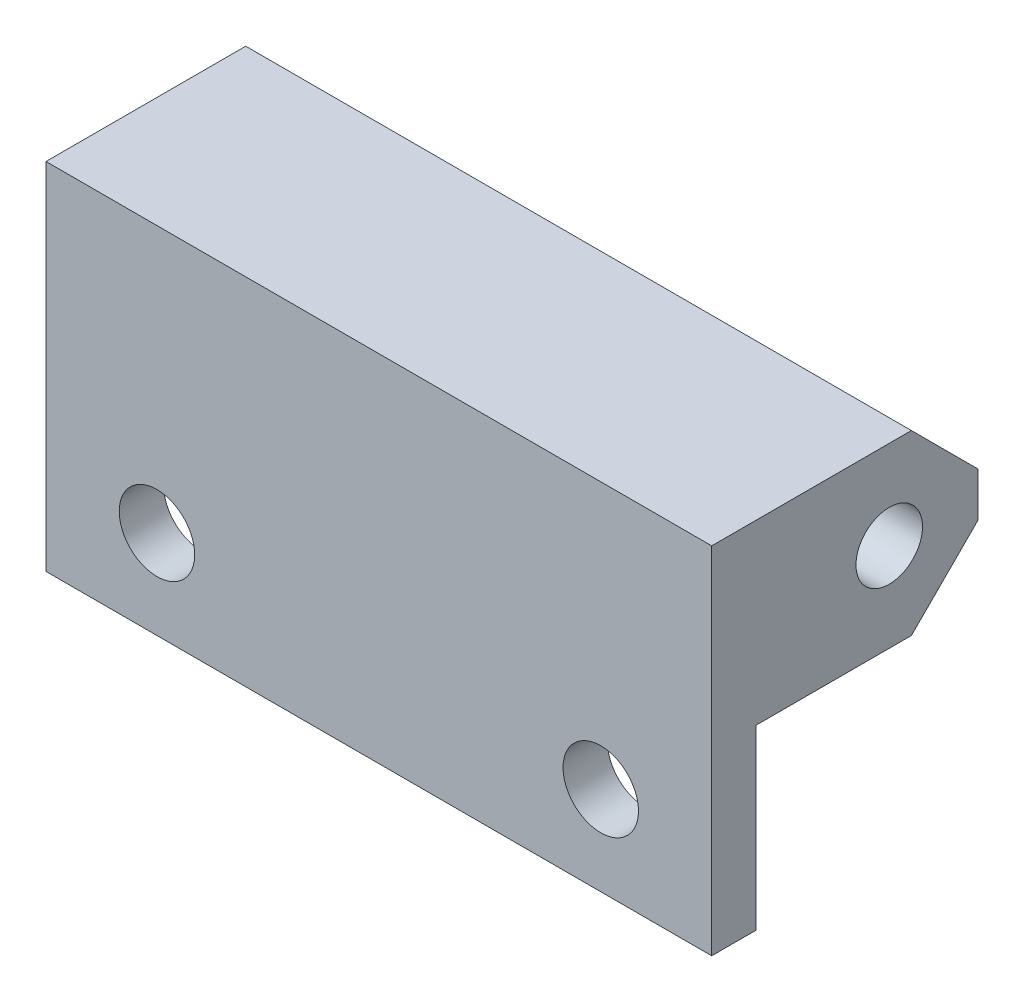
SolidWorks part; units mm, degrees
material "6061 Alloy"
ref_plane "Front Plane" through (0, 0, 0) normal (0, 0, 1) x (1, 0, 0)
ref_plane "Top Plane" through (0, 0, 0) normal (0, 1, 0) x (1, 0, 0)
ref_plane "Right Plane" through (0, 0, 0) normal (1, 0, 0) x (0, 0, -1)
sketch "Sketch1" plane through (0, 0, 0) normal (1, 0, 0) x (0, 0, -1)
  line L0 (-8, 8) -> (0, 8)
  line L1 (0, 0) -> (-6, 0)
  line L2 (-6, 0) -> (-6, -8)
  line L3 (-6, -8) -> (-8, -8)
  line L4 (-8, -8) -> (-8, 8)
  line L5 (0, 8) -> (1, 8)
  line L6 (4, 5) -> (4, 3)
  line L7 (1, 0) -> (0, 0)
  line L8 (4, 3) -> (1, 0)
  line L9 (1, 8) -> (4, 5)
  point P2 (4, 8)
  point P8 (4, 0)
  dimension "D1" = 8
  dimension "D2" = 6
  dimension "D3" = 2
  dimension "D4" = 8
  dimension "D5" = 4
  dimension "D6" = 8
extrude "Boss-Extrude1" add sketch "Sketch1" along normal mid plane 30 contours L1 L2 L3 L4 L0 L5 L9 L6 L8 L7
hole_wizard "M3 Clearance Hole1" positions "Sketch2" profile "Sketch3" hole size "M3" standard "ANSI Metric" end condition through all
sketch "Sketch2" plane through (0, 0, 6) normal (0, 0, -1) x (-1, 0, 0)
  line L1 (-15, 0) -> (-15, -8) construction
  line L2 (15, 0) -> (15, -8) construction
  line L3 (-15, 0) -> (15, 0) construction
  point P0 (-10, -4)
  point P2 (10, -4)
  dimension "D1" = 5
  dimension "D2" = 5
  dimension "D3" = 4
sketch "Sketch3" plane through (10, -4, 6) normal (1, 0, 0) x (0, 1, 0)
  line L0 (0, 0) -> (0, 2)
  line L1 (0, 2) -> (1.7, 2)
  line L2 (1.7, 2) -> (1.7, 0)
  line L5 (1.7, 0) -> (0, 0)
  line L11 (0, -6.35) -> (0, 107.95) construction
  dimension "Thru Hole Dia." = 3.4
  dimension "Thru Hole Depth" = 2
sketch "Sketch4" plane through (15, 0, 0) normal (1, 0, 0) x (0, 0, -1)
  line L1 (-8, 8) -> (1, 8) construction
  circle A0 centre (0, 4) radius 1.5
  dimension "D1" = 3
  dimension "D2" = 4
extrude "Cut-Extrude1" cut sketch "Sketch4" against normal through all and the other way through all
